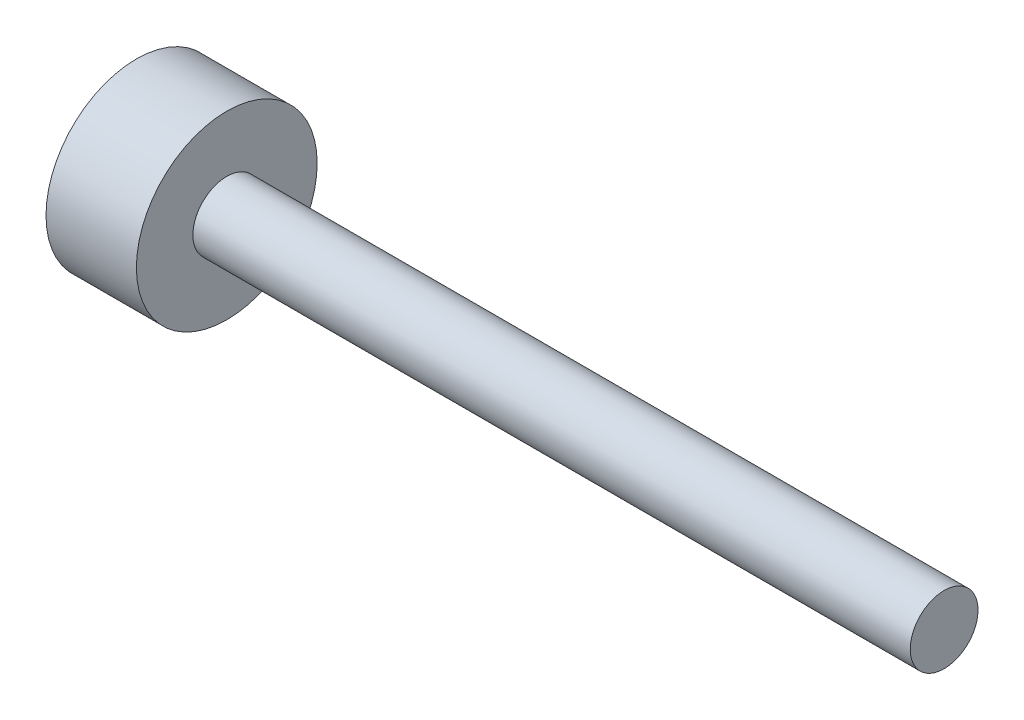
SolidWorks part; units mm, degrees
material "Delrin 2700 NC010, Low Viscosity Acetal Copolymer (SS)"
ref_plane "Front Plane" through (0, 0, 0) normal (0, 0, 1) x (1, 0, 0)
ref_plane "Top Plane" through (0, 0, 0) normal (0, 1, 0) x (1, 0, 0)
ref_plane "Right Plane" through (0, 0, 0) normal (1, 0, 0) x (0, 0, -1)
sketch "Sketch1" plane through (0, 0, 0) normal (0, 0, 1) x (1, 0, 0)
  line L0 (0, 0) -> (-17.872, 0) construction
  line L2 (0, 0) -> (-15.872, 0)
  line L3 (0, 0) -> (0, 0.75)
  line L4 (0, 0.75) -> (-15.872, 0.75)
  line L5 (-15.872, 0) -> (-15.872, 0.75)
  line L6 (-15.872, 0) -> (-17.872, 0)
  line L7 (-15.872, 0) -> (-15.872, 2)
  line L8 (-15.872, 2) -> (-17.872, 2)
  line L9 (-17.872, 0) -> (-17.872, 2)
  dimension "D1" = 2
  dimension "D2" = 15.872
  dimension "D3" = 2
  dimension "D4" = 0.75
revolve "Revolve1" add sketch "Sketch1" angle 360 about L0 region at (-7.936, 0.375, 0) region at (-16.872, 1, 0)
